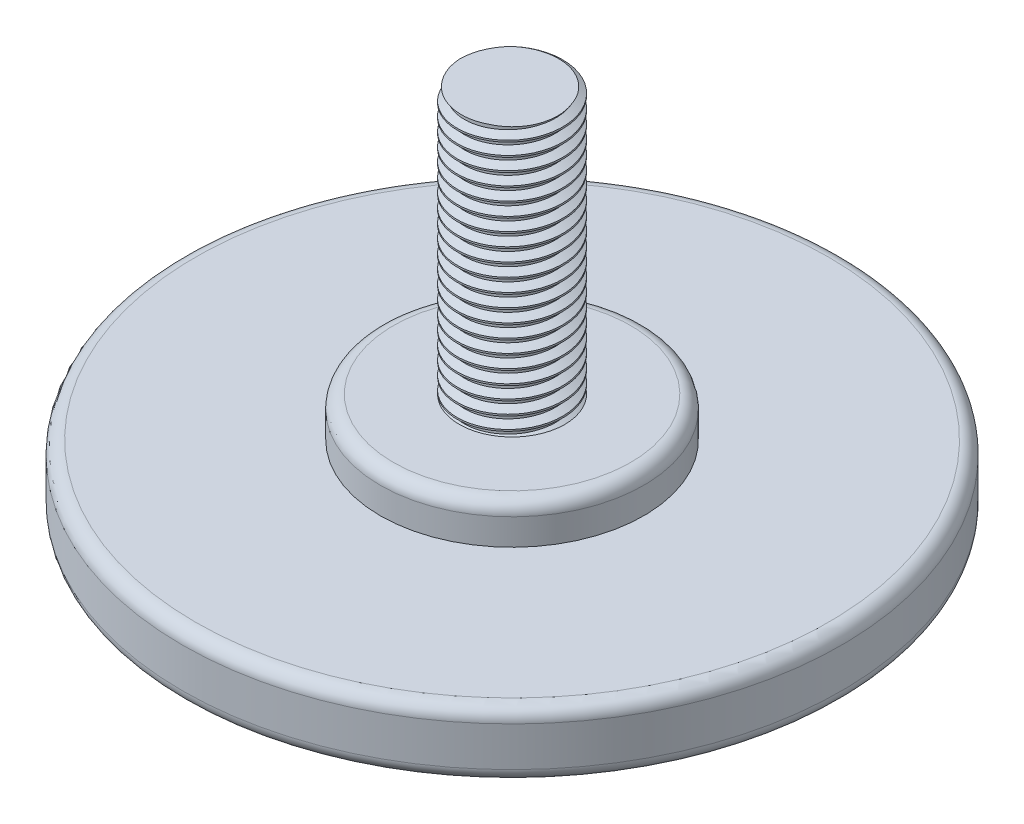
SolidWorks part; units mm, degrees
material "ABS"
ref_plane "Alzado" through (0, 0, 0) normal (0, 0, 1) x (1, 0, 0)
ref_plane "Planta" through (0, 0, 0) normal (0, 1, 0) x (1, 0, 0)
ref_plane "Vista lateral" through (0, 0, 0) normal (1, 0, 0) x (0, 0, -1)
sketch "Croquis1" plane through (0, 0, 0) normal (0, 1, 0) x (1, 0, 0)
  circle A1 centre (0, 0) radius 25
  dimension "D2" = 50
extrude "Saliente-Extruir1" add sketch "Croquis1" along normal mid plane 5
sketch "Croquis2" plane through (0, 2.5, 0) normal (0, 1, 0) x (1, 0, 0)
  circle A0 centre (0, 0) radius 10
  dimension "D1" = 20
extrude "Saliente-Extruir2" add sketch "Croquis2" along normal blind 3
sketch "Croquis3" plane through (0, 5.5, 0) normal (0, 1, 0) x (1, 0, 0)
  circle A0 centre (0, 0) radius 4
  dimension "D1" = 8
extrude "Saliente-Extruir3" add sketch "Croquis3" along normal blind 20
thread "Rosca1" pitch 1 method cut profile "Perfil de rosca1" start angle 0, offset 1, length 0, pitch 1, diameter 8
ref_plane "Plano1" through (-4, 26.5, 0) normal (0, 0, 1) x (-1, 0, 0)
sketch "Perfil de rosca1" plane through (-4, 26.5, 0) normal (0, 0, 1) x (-1, 0, 0)
  line L0 (0, 0) -> (0, 1) construction
  line L11 (0, 0) -> (0, 0.875)
  line L12 (0, 0.875) -> (-0.5413, 0.5625)
  line L13 (-0.5413, 0.5625) -> (-0.5413, 0.3125)
  line L15 (-0.5413, 0.3125) -> (0, 0)
  line L17 (-0.5413, 0.4375) -> (0, 0.4375) construction
  point P2 (0, 0)
  dimension "Pitch" = 1
  dimension "Profile_Angle" = 60
  dimension "Profile_Land" = 0.25
  dimension "Profile_Height" = 0.5413
fillet "Redondeo2" radius 1 3 edges at (0, -2.5, 25) (0, 2.5, 25) (0, 5.5, 10)
